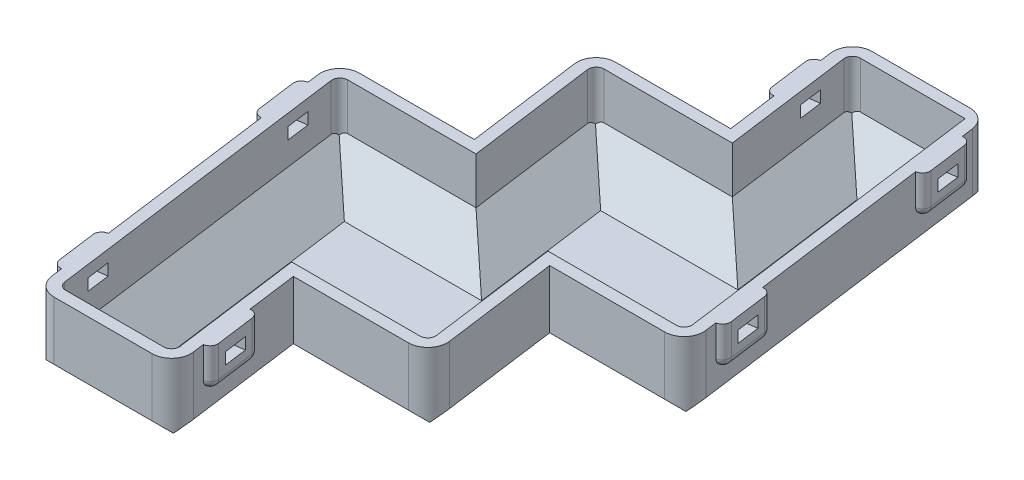
SolidWorks part; units mm, degrees
ref_plane "Front Plane" through (0, 0, 0) normal (0, 0, 1) x (1, 0, 0)
ref_plane "Top Plane" through (0, 0, 0) normal (0, 1, 0) x (1, 0, 0)
ref_plane "Right Plane" through (0, 0, 0) normal (1, 0, 0) x (0, 0, -1)
sketch "Sketch1" plane through (0, 0, 0) normal (0, 1, 0) x (1, 0, 0)
  line L12 (-23.6432, 44.6001) -> (11.6707, 44.6001)
  line L17 (-23.6432, 44.6001) -> (-11.6707, -44.6001)
  line L18 (11.6707, 44.6001) -> (23.6432, -44.6001)
  line L19 (-11.6707, -44.6001) -> (23.6432, -44.6001)
  line L20 (-5.9862, 44.6001) -> (5.9862, -44.6001) construction
  line L21 (54.2056, -9.2001) -> (18.8918, -9.2001)
  line L22 (54.2056, -9.2001) -> (42.2332, 80)
  line L23 (18.8918, -9.2001) -> (6.9193, 80)
  line L24 (42.2332, 80) -> (6.9193, 80)
  line L25 (36.5487, -9.2001) -> (24.5762, 80) construction
  line L26 (-54.2056, 9.2001) -> (-18.8918, 9.2001)
  line L27 (-54.2056, 9.2001) -> (-42.2332, -80)
  line L28 (-18.8918, 9.2001) -> (-6.9193, -80)
  line L29 (-42.2332, -80) -> (-6.9193, -80)
  line L30 (-36.5487, 9.2001) -> (-24.5762, -80) construction
  line L31 (-9.0465, -41.6001) -> (20.2136, -41.6001) construction
  line L32 (-9.0465, -41.6001) -> (-20.2136, 41.6001) construction
  line L33 (20.2136, -41.6001) -> (9.0465, 41.6001) construction
  line L34 (-20.2136, 41.6001) -> (9.0465, 41.6001) construction
  line L35 (-18.8918, 9.2001) -> (18.8918, -9.2001) construction
  line L36 (5.5836, -41.6001) -> (19.9547, -39.6712) construction
  point P7 (0, 0)
  point P20 (-5.5836, 41.6001)
  point P21 (5.5836, -41.6001)
  point P26 (14.63, 0)
  point P27 (0, 0)
  point P28 (59.1129, 11.8398)
  dimension "D1" = 90
  dimension "D2" = 29
  dimension "D3" = 160
  dimension "D4" = 3
  dimension "D5" = 3
  dimension "D6" = 82
extrude "Boss-Extrude1" add sketch "Sketch1" along normal blind 25 contours L18 | L17 L18 | L17 region at (0, 0, 0) region at (30.5625, 0, -35.3999) region at (-30.5625, 0, 35.3999)
sketch "Sketch4" plane through (0, 25, 0) normal (0, 1, 0) x (1, 0, 0)
  line L0 (-9.0465, -41.6001) -> (20.2136, -41.6001)
  line L1 (-9.0465, -41.6001) -> (-20.2136, 41.6001)
  line L2 (20.2136, -41.6001) -> (9.0465, 41.6001)
  line L3 (-20.2136, 41.6001) -> (9.0465, 41.6001)
  line L4 (21.516, -6.2001) -> (50.7761, -6.2001)
  line L5 (21.516, -6.2001) -> (10.3489, 77)
  line L6 (50.7761, -6.2001) -> (39.6089, 77)
  line L7 (10.3489, 77) -> (39.6089, 77)
  line L8 (24.9789, 77) -> (36.146, -6.2001) construction
  line L9 (-50.7761, 6.2001) -> (-21.516, 6.2001)
  line L10 (-50.7761, 6.2001) -> (-39.6089, -77)
  line L11 (-21.516, 6.2001) -> (-10.3489, -77)
  line L12 (-39.6089, -77) -> (-10.3489, -77)
  line L13 (-36.146, 6.2001) -> (-24.9789, -77) construction
  line L14 (-54.2056, 9.2001) -> (-18.8918, 9.2001) construction
  line L15 (-54.2056, 9.2001) -> (-42.2332, -80) construction
  line L16 (42.2332, 80) -> (6.9193, 80) construction
  line L17 (18.8918, -9.2001) -> (6.9193, 80) construction
  line L18 (-21.516, 6.2001) -> (-15.4622, 6.2001)
  line L19 (-9.0465, -41.6001) -> (-15.1003, -41.6001)
  line L20 (21.516, -6.2001) -> (15.4622, -6.2001)
  line L21 (9.0465, 41.6001) -> (15.1003, 41.6001)
  dimension "D1" = 3
  dimension "D2" = 3
  dimension "D3" = 3
  dimension "D4" = 3
extrude "Cut-Extrude1" cut sketch "Sketch4" against normal blind 22 contours L10 L12 L11 L9 | L19 L1 L18 L11 | L3 L1 L0 L2 | L7 L5 L4 L6 | L21 L2 L20 L5 region at (0, 25, 0) region at (-15.2812, 25, 17.7) region at (-30.5625, 25, 35.3999) region at (15.2812, 25, -17.7) region at (30.5625, 25, -35.3999)
chamfer "Chamfer1" distance 10 angle 45 24 edges at (-33.1191, 3, -6.2001) (-17.8379, 3, -23.9001) (-2.5567, 3, -41.6001) (12.7246, 3, -59.3) (24.9789, 3, -77) (45.1925, 3, -35.3999) (33.1191, 3, 6.2001) (17.8379, 3, 23.9001) (2.5567, 3, 41.6001) (-12.7246, 3, 59.3) (-24.9789, 3, 77) (-45.1925, 3, 35.3999) (24.5762, 0, -80) (9.295, 0, -62.3) (-5.9862, 0, -44.6001) (-21.2675, 0, -26.9001) (-36.5487, 0, -9.2001) (-48.2194, 0, 35.3999) (-24.5762, 0, 80) (-9.295, 0, 62.3) (5.9862, 0, 44.6001) (21.2675, 0, 26.9001) (36.5487, 0, 9.2001) (48.2194, 0, -35.3999)
fillet "Fillet1" radius 2 7 edges at (50.7761, 19, 6.2001) (20.2136, 19, 41.6001) (-10.3489, 19, 77) (-39.6089, 19, 77) (-50.7761, 19, -6.2001) (-20.2136, 19, -41.6001) (10.3489, 19, -77)
fillet "Fillet2" radius 5 8 edges at (6.9193, 17.5, -80) (-23.6432, 17.5, -44.6001) (54.2056, 17.5, 9.2001) (23.6432, 17.5, 44.6001) (-6.9193, 17.5, 80) (-42.2332, 17.5, 80) (-54.2056, 17.5, -9.2001) (42.2332, 17.5, -80)
sketch "Sketch5" plane through (-52.0334, 0, 6.9839) normal (-0.9911, 0, 0.133) x (0.133, 0, 0.9911)
  line L0 (-10.6132, 25) -> (69.2971, 25) construction
  line L1 (66.2971, 15) -> (52.2971, 15)
  line L2 (66.2971, 15) -> (66.2971, 25)
  line L3 (66.2971, 25) -> (52.2971, 25)
  line L4 (52.2971, 15) -> (52.2971, 25)
  line L5 (66.2971, 15) -> (52.2971, 25) construction
  line L6 (66.2971, 25) -> (52.2971, 15) construction
  line L7 (69.2971, 10) -> (69.2971, 25) construction
  line L8 (29.3419, 10) -> (29.3419, 25) construction
  line L9 (-10.6132, 10) -> (69.2971, 10) construction
  line L10 (-7.6132, 25) -> (6.3868, 15) construction
  line L11 (-7.6132, 15) -> (6.3868, 25) construction
  line L12 (6.3868, 15) -> (6.3868, 25)
  line L13 (-7.6132, 25) -> (6.3868, 25)
  line L14 (-7.6132, 15) -> (-7.6132, 25)
  line L15 (-7.6132, 15) -> (6.3868, 15)
  point P0 (59.2971, 20)
  point P17 (-0.6132, 20)
  dimension "D1" = 3
  dimension "D2" = 14
  dimension "D3" = 10
extrude "Boss-Extrude2" add sketch "Sketch5" along normal blind 2
sketch "Sketch10" plane through (-54.0156, 0, 7.25) normal (-0.9911, 0, 0.133) x (0.133, 0, 0.9911)
  line L0 (52.2971, 15) -> (52.2971, 25) construction
  line L1 (62.2971, 19) -> (56.2971, 19)
  line L2 (62.2971, 19) -> (62.2971, 22)
  line L3 (62.2971, 22) -> (56.2971, 22)
  line L4 (56.2971, 19) -> (56.2971, 22)
  line L5 (62.2971, 19) -> (56.2971, 22) construction
  line L6 (62.2971, 22) -> (56.2971, 19) construction
  line L7 (66.2971, 25) -> (52.2971, 25) construction
  line L8 (29.3419, 25) -> (29.3419, 10) construction
  line L9 (-3.6132, 22) -> (2.3868, 19) construction
  line L10 (-3.6132, 19) -> (2.3868, 22) construction
  line L11 (2.3868, 19) -> (2.3868, 22)
  line L12 (-3.6132, 22) -> (2.3868, 22)
  line L13 (-3.6132, 19) -> (-3.6132, 22)
  line L14 (-3.6132, 19) -> (2.3868, 19)
  point P0 (59.2971, 20.5)
  point P17 (-0.6132, 20.5)
  dimension "D1" = 6
  dimension "D2" = 3
  dimension "D3" = 4
  dimension "D4" = 3
extrude "Cut-Extrude3" cut sketch "Sketch10" against normal up to surface (5 mm away) and the other way through all up to face at (-45.1568, 19, 35.666)
sketch "Sketch6" plane through (-17.3445, 0, 2.328) normal (0.9911, 0, -0.133) x (-0.133, 0, -0.9911)
  line L0 (-42.6511, 25) -> (-72.6526, 25) construction
  line L5 (-55.6526, 15) -> (-69.6526, 15)
  line L6 (-55.6526, 15) -> (-55.6526, 25)
  line L7 (-55.6526, 25) -> (-69.6526, 25)
  line L8 (-69.6526, 15) -> (-69.6526, 25)
  line L9 (-55.6526, 15) -> (-69.6526, 25) construction
  line L10 (-55.6526, 25) -> (-69.6526, 15) construction
  line L11 (-72.6526, 25) -> (-72.6526, 10) construction
  point P0 (-62.6526, 20)
  dimension "D1" = 3
  dimension "D2" = 14
  dimension "D3" = 10
extrude "Boss-Extrude4" add sketch "Sketch6" along normal blind 2
sketch "Sketch7" plane through (52.0334, 0, -6.9839) normal (0.9911, 0, -0.133) x (-0.133, 0, -0.9911)
  line L0 (-10.6132, 25) -> (69.2971, 25) construction
  line L1 (52.2971, 15) -> (66.2971, 15)
  line L2 (52.2971, 15) -> (52.2971, 25)
  line L3 (52.2971, 25) -> (66.2971, 25)
  line L4 (66.2971, 15) -> (66.2971, 25)
  line L5 (52.2971, 15) -> (66.2971, 25) construction
  line L6 (52.2971, 25) -> (66.2971, 15) construction
  line L8 (69.2971, 10) -> (69.2971, 25) construction
  line L9 (29.3419, 25) -> (29.3419, 10) construction
  line L10 (-10.6132, 25) -> (69.2971, 25) construction
  line L11 (-10.6132, 10) -> (69.2971, 10) construction
  line L12 (6.3868, 25) -> (-7.6132, 15) construction
  line L13 (6.3868, 15) -> (-7.6132, 25) construction
  line L14 (-7.6132, 15) -> (-7.6132, 25)
  line L15 (6.3868, 25) -> (-7.6132, 25)
  line L16 (6.3868, 15) -> (6.3868, 25)
  line L17 (6.3868, 15) -> (-7.6132, 15)
  point P0 (59.2971, 20)
  point P19 (-0.6132, 20)
  dimension "D1" = 3
  dimension "D2" = 14
  dimension "D3" = 10
extrude "Boss-Extrude5" add sketch "Sketch7" along normal blind 2
sketch "Sketch11" plane through (54.0156, 0, -7.25) normal (0.9911, 0, -0.133) x (-0.133, 0, -0.9911)
  line L5 (-7.6132, 25) -> (-7.6132, 15) construction
  line L6 (2.3868, 19) -> (-3.6132, 19)
  line L7 (2.3868, 19) -> (2.3868, 22)
  line L8 (2.3868, 22) -> (-3.6132, 22)
  line L9 (-3.6132, 19) -> (-3.6132, 22)
  line L10 (2.3868, 19) -> (-3.6132, 22) construction
  line L11 (2.3868, 22) -> (-3.6132, 19) construction
  line L12 (7.6132, 25) -> (-6.3868, 25) construction
  line L13 (29.3419, 25) -> (29.3419, 10) construction
  line L14 (6.3868, 25) -> (52.2971, 25) construction
  line L15 (-10.6132, 10) -> (69.2971, 10) construction
  line L16 (56.2971, 22) -> (62.2971, 19) construction
  line L17 (56.2971, 19) -> (62.2971, 22) construction
  line L18 (62.2971, 19) -> (62.2971, 22)
  line L19 (56.2971, 22) -> (62.2971, 22)
  line L20 (56.2971, 19) -> (56.2971, 22)
  line L21 (56.2971, 19) -> (62.2971, 19)
  point P0 (-0.6132, 20.5)
  point P19 (59.2971, 20.5)
  dimension "D1" = 4
  dimension "D2" = 3
  dimension "D3" = 6
  dimension "D4" = 3
extrude "Cut-Extrude4" cut sketch "Sketch11" against normal up to surface (5 mm away) and the other way through all up to face at (45.0404, 19, -36.533)
sketch "Sketch8" plane through (17.3445, 0, -2.328) normal (-0.9911, 0, 0.133) x (0.133, 0, 0.9911)
  line L0 (-42.6511, 25) -> (-72.6526, 25) construction
  line L1 (-55.6526, 15) -> (-69.6526, 15)
  line L2 (-55.6526, 15) -> (-55.6526, 25)
  line L3 (-55.6526, 25) -> (-69.6526, 25)
  line L4 (-69.6526, 15) -> (-69.6526, 25)
  line L5 (-55.6526, 15) -> (-69.6526, 25) construction
  line L6 (-55.6526, 25) -> (-69.6526, 15) construction
  line L7 (-72.6526, 25) -> (-72.6526, 10) construction
  point P0 (-62.6526, 20)
  dimension "D1" = 3
  dimension "D2" = 10
  dimension "D3" = 14
extrude "Boss-Extrude6" add sketch "Sketch8" along normal blind 2
sketch "Sketch9" plane through (15.3622, 0, -2.0619) normal (-0.9911, 0, 0.133) x (0.133, 0, 0.9911)
  line L0 (-69.6526, 25) -> (-69.6526, 15) construction
  line L1 (-65.6526, 19) -> (-59.6526, 19)
  line L2 (-65.6526, 19) -> (-65.6526, 22)
  line L3 (-65.6526, 22) -> (-59.6526, 22)
  line L4 (-59.6526, 19) -> (-59.6526, 22)
  line L5 (-65.6526, 19) -> (-59.6526, 22) construction
  line L6 (-65.6526, 22) -> (-59.6526, 19) construction
  line L7 (-55.6526, 25) -> (-69.6526, 25) construction
  point P0 (-62.6526, 20.5)
  dimension "D1" = 6
  dimension "D2" = 3
  dimension "D3" = 4
  dimension "D4" = 3
extrude "Cut-Extrude2" cut sketch "Sketch9" against normal up to surface (5 mm away) and the other way through all up to face at (12.8766, 19, -58.167)
sketch "Sketch12" plane through (-15.3622, 0, 2.0619) normal (0.9911, 0, -0.133) x (-0.133, 0, -0.9911)
  line L0 (-66.2971, 25) -> (-52.2971, 25) construction
  line L1 (-59.6526, 19) -> (-65.6526, 19)
  line L2 (-59.6526, 19) -> (-59.6526, 22)
  line L3 (-59.6526, 22) -> (-65.6526, 22)
  line L4 (-65.6526, 19) -> (-65.6526, 22)
  line L5 (-59.6526, 19) -> (-65.6526, 22) construction
  line L6 (-59.6526, 22) -> (-65.6526, 19) construction
  line L7 (-55.6526, 15) -> (-55.6526, 25) construction
  point P0 (-62.6526, 20.5)
  dimension "D1" = 3
  dimension "D2" = 4
  dimension "D3" = 3
  dimension "D4" = 6
extrude "Cut-Extrude5" cut sketch "Sketch12" against normal up to surface (5 mm away) up to face at (-12.8766, 19, 58.167)
fillet "Fillet3" radius 2 18 edges at (6.0965, 20, -71.0955) (7.0277, 15, -64.1577) (7.9589, 20, -57.2199) (-55.0284, 20, -0.2956) (-54.0972, 15, 6.6422) (-53.166, 20, 13.58) (-47.0587, 20, 59.0823) (-46.1275, 15, 66.0201) (-45.1963, 20, 72.9579) (-6.0965, 20, 71.0955) (-7.0277, 15, 64.1577) (-7.9589, 20, 57.2199) (55.0284, 20, 0.2956) (54.0972, 15, -6.6422) (53.166, 20, -13.58) (47.0587, 20, -59.0823) (45.1963, 20, -72.9579) (46.1275, 15, -66.0201)
